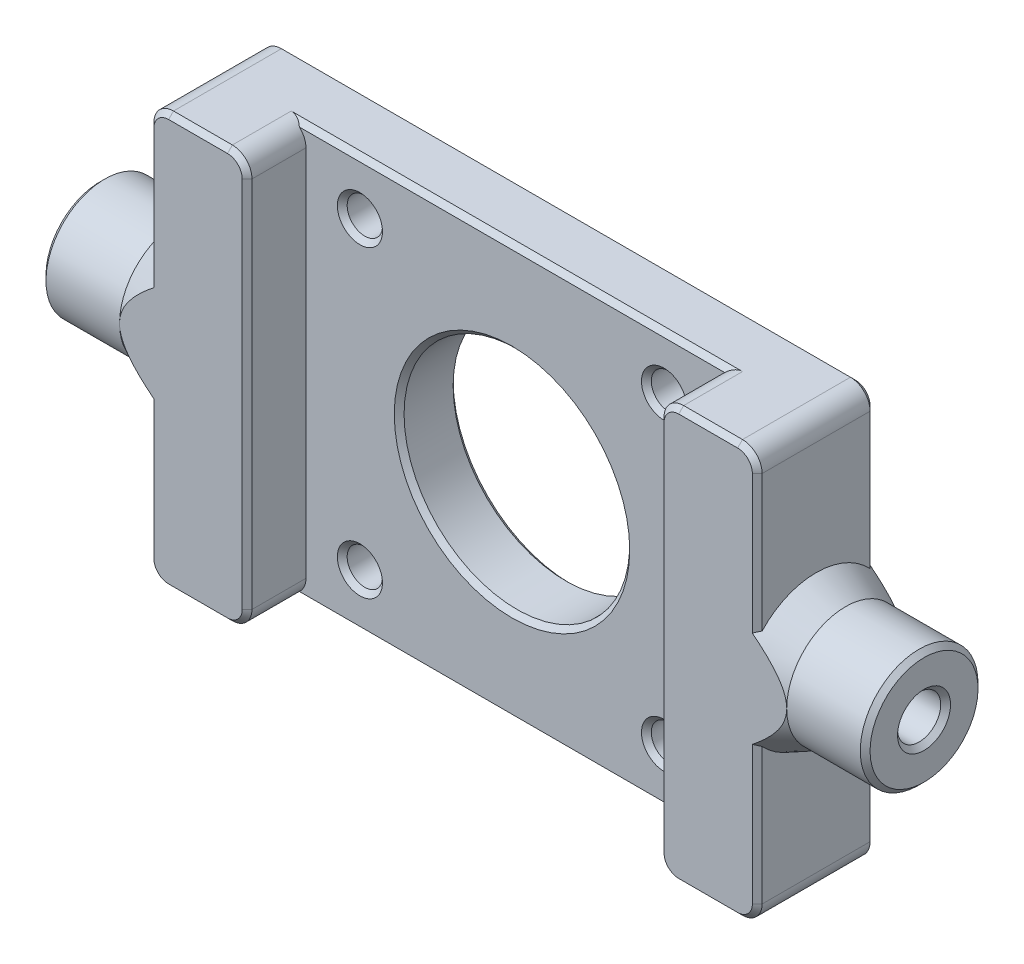
SolidWorks part; units mm, degrees
ref_plane "Front" through (0, 0, 0) normal (0, 0, 1) x (1, 0, 0)
ref_plane "Top" through (0, 0, 0) normal (0, 1, 0) x (1, 0, 0)
ref_plane "Right" through (0, 0, 0) normal (1, 0, 0) x (0, 0, -1)
sketch "Skizze1" plane through (0, 0, 0) normal (0, 0, 1) x (1, 0, 0)
  line L0 (21, 21) -> (31, 21)
  line L1 (-21, -21) -> (21, -21)
  line L2 (-21, -21) -> (-21, 21) construction
  line L3 (-21, 21) -> (21, 21)
  line L4 (21, -21) -> (21, 21) construction
  line L5 (-21, -21) -> (21, 21) construction
  line L6 (-21, 21) -> (21, -21) construction
  line L7 (31, 21) -> (31, -21)
  line L8 (31, -21) -> (21, -21)
  line L9 (0, 0) -> (0, 21) construction
  line L10 (-31, -21) -> (-21, -21)
  line L11 (-31, 21) -> (-31, -21)
  line L12 (-21, 21) -> (-31, 21)
  point P0 (0, 0)
  dimension "D1" = 42
  dimension "D2" = 10
extrude "Aufsatz-Linear austragen1" add sketch "Skizze1" along normal blind 6
sketch "Skizze2" plane through (0, 0, 6) normal (0, 0, 1) x (1, 0, 0)
  line L0 (21, 21) -> (21, -21)
  line L1 (31, 21) -> (-31, 21) construction
  line L2 (-31, -21) -> (31, -21) construction
  line L3 (21, -21) -> (31, -21)
  line L4 (31, -21) -> (31, 21)
  line L5 (31, 21) -> (21, 21)
  line L6 (0, 0) -> (0, 25.5204) construction
  line L7 (-31, -21) -> (-31, 21)
  line L8 (-21, -21) -> (-31, -21)
  line L9 (-21, 21) -> (-21, -21)
  line L10 (-31, 21) -> (-21, 21)
  dimension "D1" = 42
extrude "Aufsatz-Linear austragen2" add sketch "Skizze2" along normal offset from surface (6 mm away) 12 up to face at (0, 0, 0)
sketch "Skizze3" plane through (31, 0, 0) normal (1, 0, 0) x (0, 0, -1)
  line L0 (0, 0) -> (-12, 0) construction
  line L1 (0, -21) -> (0, 21) construction
  line L2 (-12, 21) -> (-12, -21) construction
  circle A0 centre (-6, 0) radius 6
extrude "Aufsatz-Linear austragen3" add sketch "Skizze3" along normal blind 11
sketch "Skizze5" plane through (42, 0, 0) normal (1, 0, 0) x (0, 0, -1)
  circle A0 centre (-6, 0) radius 2.2
  dimension "D1" = 4.4
extrude "Schnitt-Linear austragen2" cut sketch "Skizze5" against normal blind 10
mirror "Spiegeln1" about plane through (0, 0, 0) normal (1, 0, 0) of "Schnitt-Linear austragen2", "Aufsatz-Linear austragen3"
sketch "Skizze4" plane through (0, 0, 6) normal (0, 0, 1) x (1, 0, 0)
  line L1 (-15.5, -15.5) -> (15.5, -15.5) construction
  line L2 (-15.5, -15.5) -> (-15.5, 15.5) construction
  line L3 (-15.5, 15.5) -> (15.5, 15.5) construction
  line L4 (15.5, -15.5) -> (15.5, 15.5) construction
  line L5 (-15.5, -15.5) -> (15.5, 15.5) construction
  line L6 (-15.5, 15.5) -> (15.5, -15.5) construction
  circle A0 centre (0, 0) radius 11.5
  circle A1 centre (-15.5, 15.5) radius 1.8
  circle A2 centre (15.5, 15.5) radius 1.8
  circle A3 centre (15.5, -15.5) radius 1.8
  circle A4 centre (-15.5, -15.5) radius 1.8
  dimension "D1" = 23
  dimension "D3" = 3.6
  dimension "D2" = 31
extrude "Schnitt-Linear austragen1" cut sketch "Skizze4" against normal blind 8
chamfer "Fase1" distance 1.5 distance2 3 2 edges at (31, -6, 6) (31, 6, 6)
chamfer "Fase2" distance 3 distance2 1.5 2 edges at (-31, -6, 6) (-31, 6, 6) first distance on face at (-42, 6, 6)
fillet "Verrundung1" radius 2 8 edges at (21, -21, 9) (21, 21, 9) (-21, 21, 9) (-31, -21, 6) (31, -21, 6) (-31, 21, 6) (31, 21, 6) (-21, -21, 9)
chamfer "Fase3" distance 0.5 angle 45 44 edges at (-13.7, 15.5, 6) (-17.3, 15.5, 0) (-13.7, -15.5, 6) (-17.3, -15.5, 0) (17.3, -15.5, 6) (13.7, -15.5, 0) (17.3, 15.5, 6) (13.7, 15.5, 0) (11.5, 0, 6) (-11.5, 0, 0) (-42, 6, 6) (42, 6, 6) (-31, 11.75, 12) (-26, 21, 12) (-21, 0, 12) (-31, -11.75, 12) (-26, -21, 12) (31, -11.75, 12) (26, -21, 12) (31, 11.75, 12) (26, 21, 12) (21, 0, 12) (-31, -11.75, 0) (0, -21, 0) (31, -11.75, 0) (31, 11.75, 0) (0, 21, 0) (-31, 11.75, 0) (-30.4142, 20.4142, 12) (-21.5858, 20.4142, 12) (-30.4142, -20.4142, 12) (30.4142, -20.4142, 12) (30.4142, 20.4142, 12) (21.5858, -20.4142, 12) (21.5858, 20.4142, 12) (-30.4142, -20.4142, 0) (30.4142, -20.4142, 0) (30.4142, 20.4142, 0) (-30.4142, 20.4142, 0) (0, 21, 6) (0, -21, 6) (-21.5858, -20.4142, 12) (42, 2.2, 6) (-42, 2.2, 6)
